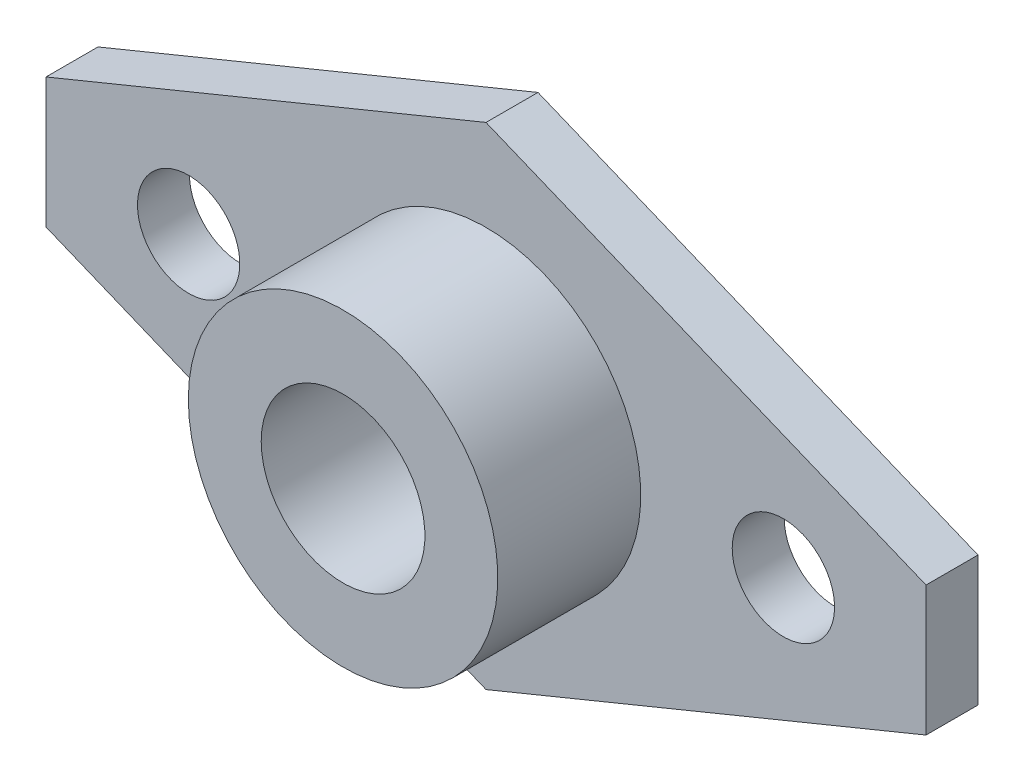
SolidWorks part; units mm, degrees
ref_plane "Front Plane" through (0, 0, 0) normal (0, 0, 1) x (1, 0, 0)
ref_plane "Top Plane" through (0, 0, 0) normal (0, 1, 0) x (1, 0, 0)
ref_plane "Right Plane" through (0, 0, 0) normal (1, 0, 0) x (0, 0, -1)
sketch "Sketch1" plane through (0, 0, 0) normal (0, 0, 1) x (1, 0, 0)
  line L0 (-21.5, 3.175) -> (0, 12)
  line L2 (21.5, 0) -> (21.5, -3.175)
  line L4 (-21.5, -3.175) -> (-21.5, 3.175)
  line L13 (21.5, 0) -> (21.5, 3.175)
  line L15 (0, 12) -> (21.5, 3.175)
  line L16 (21.5, -3.175) -> (0, -12)
  line L17 (0, -12) -> (-21.5, -3.175)
  circle A0 centre (0, 0) radius 7.5608
  circle A1 centre (0, 0) radius 4
  circle A2 centre (-14.5304, 0) radius 2.5
  circle A3 centre (14.5304, 0) radius 2.5
  point P0 (0, 0)
  point P9 (-21.5, 0)
extrude "Boss-Extrude1" add sketch "Sketch1" along normal blind 2.54 contours L15 L13 L2 L16 L17 L4 L0
extrude "Boss-Extrude2" add sketch "Sketch1<4>" along normal blind 9.525 contours A0
sketch "Sketch1<4>" plane through (0, 0, 0) normal (0, 0, 1) x (1, 0, 0) same geometry as "Sketch1"
extrude "Cut-Extrude1" cut sketch "Sketch1<8>" against normal blind 9.525 and the other way through all contours A1 | A3 | A2 region at (0, 0, 0) region at (-14.5304, 0, 0) region at (14.5304, 0, 0)
sketch "Sketch1<8>" plane through (0, 0, 0) normal (0, 0, 1) x (1, 0, 0) same geometry as "Sketch1"
